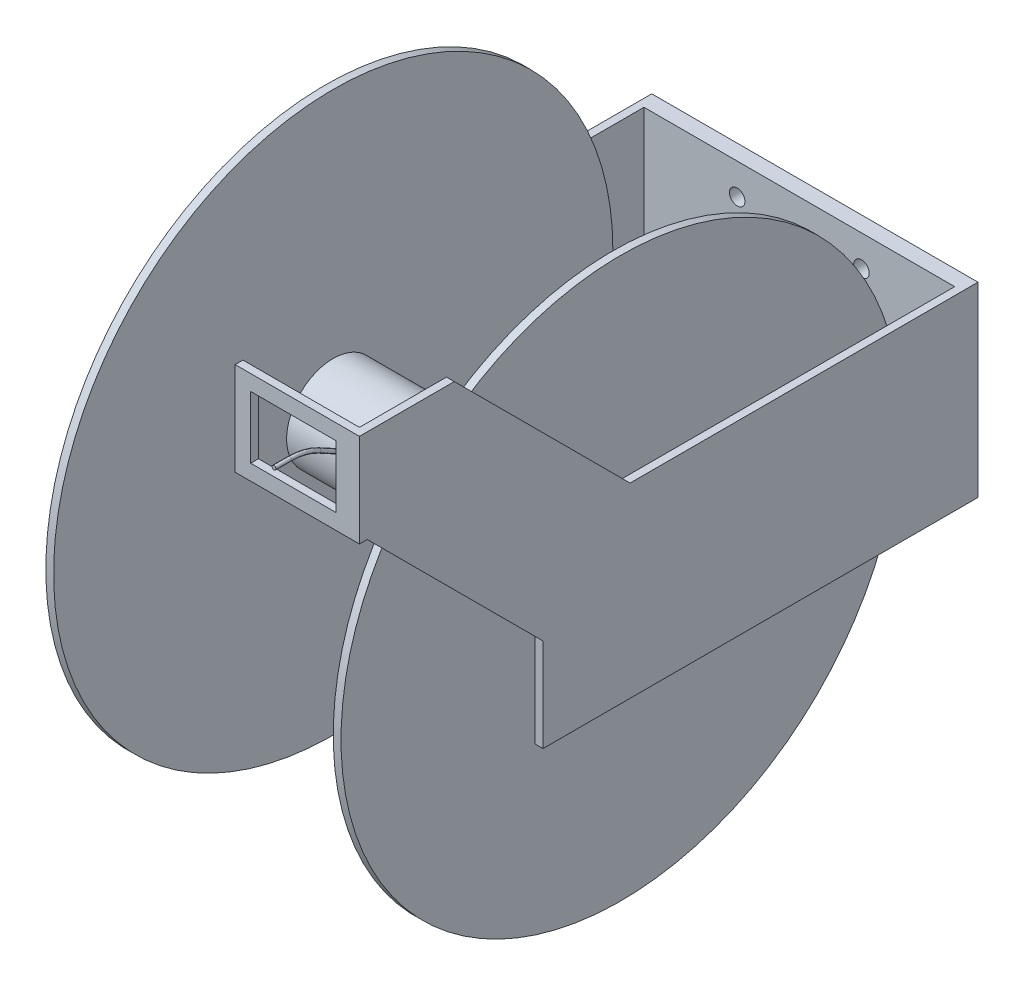
SolidWorks part; units mm, degrees
material "1060 Alloy"
ref_plane "Front Plane" through (0, 0, 0) normal (0, 0, 1) x (1, 0, 0)
ref_plane "Top Plane" through (0, 0, 0) normal (0, 1, 0) x (1, 0, 0)
ref_plane "Right Plane" through (0, 0, 0) normal (1, 0, 0) x (0, 0, -1)
sketch "Sketch1" plane through (0, 0, 0) normal (1, 0, 0) x (0, 0, -1)
  circle A0 centre (0, 0) radius 228.6
  dimension "D1" = 457.2
extrude "Boss-Extrude1" add sketch "Sketch1" along normal blind 6.35
sketch "Sketch2" plane through (6.35, 0, 0) normal (1, 0, 0) x (0, 0, -1)
  circle A0 centre (0, 0) radius 38.1
extrude "Boss-Extrude2" add sketch "Sketch2" along normal blind 228.6
sketch "Sketch3" plane through (234.95, 0, 0) normal (1, 0, 0) x (0, 0, -1)
  circle A0 centre (0, 0) radius 228.6
  dimension "D1" = 457.2
extrude "Boss-Extrude3" add sketch "Sketch3" along normal blind 6.35
sketch "Sketch4" plane through (241.3, 0, 0) normal (1, 0, 0) x (0, 0, -1)
  circle A0 centre (0, 0) radius 38.1
  dimension "D1" = 76.2
extrude "Boss-Extrude4" add sketch "Sketch4" along normal blind 6.35
sketch "Sketch5" plane through (0, 0, 0) normal (-1, 0, 0) x (0, 0, 1)
  circle A0 centre (0, 0) radius 38.1
  dimension "D1" = 76.2
extrude "Boss-Extrude5" add sketch "Sketch5" along normal blind 6.35
sketch "Sketch6" plane through (247.65, 0, 0) normal (1, 0, 0) x (0, 0, -1)
  line L4 (-76.2, -76.2) -> (-76.2, 0)
  line L13 (-5.0285, 76.2) -> (76.2, 76.2)
  line L16 (-76.2, 0) -> (-219.8841, 143.6841)
  line L17 (-5.0285, 76.2) -> (-148.7126, 219.8841)
  line L19 (-219.8841, 219.8841) -> (-219.8841, 143.6841)
  line L20 (76.2, 76.2) -> (76.2, -76.2)
  line L29 (76.2, -76.2) -> (-76.2, -76.2)
  line L30 (-219.8841, 219.8841) -> (-148.7126, 219.8841)
  dimension "D1" = 135
  dimension "D2" = 152.4
  dimension "D5" = 203.2
  dimension "D3" = 152.4
  dimension "D4" = 76.2
extrude "Boss-Extrude6" add sketch "Sketch6" along normal blind 6.35
sketch "Sketch7" plane through (254, 0, 0) normal (1, 0, 0) x (0, 0, -1)
  line L0 (76.2, 76.2) -> (76.2, -76.2)
  line L1 (76.2, 76.2) -> (279.4, 76.2)
  line L2 (76.2, -76.2) -> (279.4, -76.2)
  line L3 (279.4, 76.2) -> (279.4, -76.2)
  dimension "D1" = 203.2
extrude "Boss-Extrude7" add sketch "Sketch7" against normal blind 6.35
sketch "Sketch8" plane through (-6.35, 0, 0) normal (-1, 0, 0) x (0, 0, 1)
  line L1 (-76.2, -76.2) -> (76.2, -76.2)
  line L3 (-76.2, 76.2) -> (76.2, 76.2)
  line L4 (76.2, -76.2) -> (76.2, 76.2)
  line L5 (-76.2, -76.2) -> (76.2, 76.2) construction
  line L6 (-76.2, 76.2) -> (76.2, -76.2) construction
  line L7 (-76.2, 76.2) -> (-279.4, 76.2)
  line L8 (-76.2, -76.2) -> (-279.4, -76.2)
  line L9 (-279.4, 76.2) -> (-279.4, -76.2)
  point P0 (0, 0)
  dimension "D1" = 152.4
  dimension "D2" = 152.4
  dimension "D3" = 203.2
extrude "Boss-Extrude8" add sketch "Sketch8" along normal blind 6.35
sketch "Sketch9" plane through (247.65, 0, 0) normal (-1, 0, 0) x (0, 0, 1)
  line L0 (-279.4, 76.2) -> (-266.7, 76.2)
  line L1 (-279.4, 76.2) -> (-279.4, -75.4351)
  line L2 (-266.7, 76.2) -> (-266.7, -75.4351)
  line L3 (-279.4, -75.4351) -> (-266.7, -75.4351)
  line L4 (-279.4, 76.2) -> (5.0285, 76.2) construction
  dimension "D1" = 12.7
extrude "Boss-Extrude9" add sketch "Sketch9" along normal up to surface (254 mm away) up to face at (-6.35, 0, 38.1)
sketch "Sketch10" plane through (0, 0, -279.4) normal (0, 0, -1) x (-1, 0, 0)
  line L0 (12.7, 76.2) -> (-254, 76.2) construction
  line L1 (-120.65, 76.2) -> (-120.65, -75.4351) construction
  line L2 (6.35, -75.4351) -> (-247.65, -75.4351) construction
  circle A0 centre (-171.45, 50.8) radius 6.35
  circle A1 centre (-69.85, 50.8) radius 6.35
  circle A2 centre (-69.85, -50.8) radius 6.35
  circle A3 centre (-171.45, -50.8) radius 6.35
  dimension "D1" = 12.7
  dimension "D2" = 25.4
  dimension "D5" = 50.8
  dimension "D3" = 2
  dimension "D4" = 2
extrude "Cut-Extrude1" cut sketch "Sketch10" against normal up to surface (12.7 mm away) up to face at (120.65, 0.3824, -266.7)
sketch "Sketch11" plane through (0, 0, 219.8841) normal (0, 0, 1) x (1, 0, 0)
  line L1 (254, 143.6841) -> (152.4, 143.6841)
  line L2 (254, 219.8841) -> (152.4, 219.8841)
  line L3 (152.4, 143.6841) -> (152.4, 219.8841)
  line L5 (165.1, 207.1841) -> (234.95, 207.1841)
  line L6 (165.1, 207.1841) -> (165.1, 156.3841)
  line L7 (165.1, 156.3841) -> (234.95, 156.3841)
  line L9 (234.95, 207.1841) -> (234.95, 156.3841)
  line L10 (254, 219.8841) -> (254, 143.6841) construction
  line L11 (254, 219.8841) -> (254, 143.6841)
  dimension "D1" = 101.6
  dimension "D2" = 12.7
  dimension "D3" = 12.7
  dimension "D4" = 12.7
  dimension "D5" = 19.05
extrude "Boss-Extrude10" add sketch "Sketch11" along normal blind 6.35 contours L11 L1 L3 L2 | L5 L9 L7 L6
ref_plane "Plane1" through (203.2, 0, 0) normal (-1, 0, 0) x (0, 0, 1)
sketch "Sketch12" plane through (203.2, 0, 0) normal (-1, 0, 0) x (0, 0, 1)
  line L0 (-38.1, 0) -> (-38.1, 12.3175)
  line L1 (-11.906, 56.2865) -> (208.745, 175.7531)
  line L2 (219.8841, 219.8841) -> (219.8841, 143.6841) construction
  line L3 (232.5511, 181.7841) -> (245.2841, 181.7841)
  circle A0 centre (0, 0) radius 38.1 construction
  arc A1 (-38.1, 12.3175) -> (-11.906, 56.2865) centre (11.9, 12.3175) cw
  arc A2 (208.745, 175.7531) -> (232.5511, 181.7841) centre (232.5511, 131.7841) cw
  point P12 (219.8841, 181.7841)
  dimension "D1" = 50
  dimension "D3" = 50
  dimension "D2" = 25.4
sketch "Sketch13" plane through (0, 0, 0) normal (0, 1, 0) x (1, 0, 0)
  circle A0 centre (203.2, 38.1) radius 1.5875
  dimension "D1" = 3.175
sweep "Sweep1" add profiles "Sketch13" path "Sketch12"
